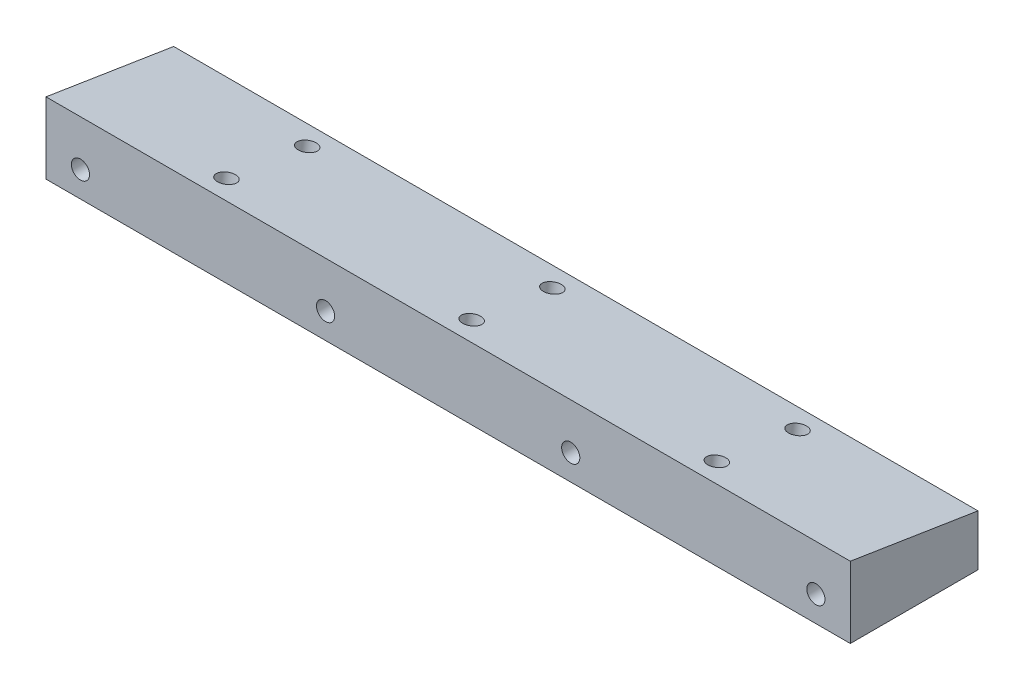
SolidWorks part; units mm, degrees
material "6061-T6 (SS)"
ref_plane "XY" through (0, 0, 0) normal (0, 0, 1) x (1, 0, 0)
ref_plane "XZ" through (0, 0, 0) normal (0, 1, 0) x (1, 0, 0)
ref_plane "YZ" through (0, 0, 0) normal (1, 0, 0) x (0, 0, -1)
ref_axis "X" through (-5, 0, 0) along (1, 0, 0)
ref_axis "Y" through (0, -6.6675, 0) along (0, 1, 0)
ref_axis "Z" through (0, 0, 6.6675) along (0, 0, -1)
sketch "Sketch1" plane through (0, 0, 0) normal (0, 0, 1) x (1, 0, 0)
  line L1 (0, 0) -> (100, 0)
  line L2 (0, 0) -> (0, -6.35)
  line L3 (0, -6.35) -> (100, -6.35)
  line L4 (100, 0) -> (100, -6.35)
  dimension "D1" = 100
  dimension "D2" = 6.35
extrude "Boss-Extrude1" add sketch "Sketch1" along normal blind 15.875
hole_wizard "#4-40 Tapped Hole1" positions "Sketch2" profile "Sketch3" tap size "#4-40" standard "ANSI Inch" end condition through all
sketch "Sketch2" plane through (0, 0, 0) normal (0, 0, -1) x (-1, 0, 0)
  line L0 (-100, -3.175) -> (-95.72, -3.175) construction
  line L1 (-100, 0) -> (-100, -6.35) construction
  line L2 (-95.72, -3.175) -> (-65.24, -3.175) construction
  line L3 (-65.24, -3.175) -> (-34.76, -3.175) construction
  line L4 (-34.76, -3.175) -> (-4.28, -3.175) construction
  line L5 (-4.28, -3.175) -> (0, -3.175) construction
  line L6 (0, 0) -> (0, -6.35) construction
  point P0 (-95.72, -3.175)
  point P2 (-4.28, -3.175)
  point P4 (-34.76, -3.175)
  point P6 (-65.24, -3.175)
  point P25 (-95.6996, -4.4429)
  dimension "D2" = 30.48
sketch "Sketch3" plane through (95.72, -3.175, 0) normal (1, 0, 0) x (0, 1, 0)
  line L0 (0, 0) -> (0, 15.875)
  line L1 (0, 15.875) -> (1.1303, 15.875)
  line L2 (1.1303, 15.875) -> (1.1303, 0)
  line L5 (1.1303, 0) -> (0, 0)
  line L11 (0, -6.35) -> (0, 107.95) construction
  dimension "Thru Tap Drill Dia." = 2.2606
  dimension "Thru Tap Drill Depth" = 15.875
cosmetic thread "Hole Thread1" parameters "D2"=2.8448
cosmetic thread "Hole Thread2" parameters "D2"=2.8448
cosmetic thread "Hole Thread3" parameters "D2"=2.8448
cosmetic thread "Hole Thread4" parameters "D2"=2.8448
sketch "Sketch4" plane through (100, 0, 0) normal (1, 0, 0) x (0, 0, -1)
  line L0 (0, 0) -> (-15.875, 2.5144)
  line L1 (-15.875, 2.5144) -> (-15.875, 0)
  line L2 (-15.875, -6.35) -> (-15.875, 0) construction
  line L3 (-15.875, 0) -> (0, 0) construction
  line L4 (-15.875, 0) -> (0, 0)
  dimension "D1" = 9
extrude "Boss-Extrude2" add sketch "Sketch4" against normal through all
hole_wizard "#4-40 Tapped Hole2" positions "Sketch5" profile "Sketch6" tap size "#4-40" standard "ANSI Inch" end condition through all
sketch "Sketch5" plane through (0, 0, 0) normal (0, 0.9877, -0.1564) x (1, 0, 0)
  line L0 (80.48, -13.1164) -> (80.48, -2.9564) construction
  line L3 (50, -13.1164) -> (50, -2.9564) construction
  line L6 (19.52, -13.1164) -> (19.52, -2.9564) construction
  line L11 (19.52, -8.0364) -> (50, -8.0364) construction
  line L12 (50, -8.0364) -> (80.48, -8.0364) construction
  line L14 (65.24, 0) -> (65.24, -8.0364)
  line L15 (100, 0) -> (0, 0) construction
  line L16 (100, -8.0364) -> (80.48, -8.0364)
  line L17 (100, 0) -> (100, -16.0729) construction
  ellipse E0 centre (65.24, 0.4967) end of major axis (66.3703, 0.4967) minor radius 0.1768 construction
  ellipse E1 centre (65.24, 0.4967) end of major axis (66.3703, 0.4967) minor radius 0.1768
  point P0 (80.48, -13.1164)
  point P2 (80.48, -2.9564)
  point P4 (50, -13.1164)
  point P6 (50, -2.9564)
  point P8 (19.52, -13.1164)
  point P10 (19.52, -2.9564)
  point P61 (100, -9.6437)
  dimension "D1" = 30.48
  dimension "D2" = 10.16
sketch "Sketch6" plane through (80.48, 2.0519, 12.955) normal (1, 0, 0) x (0, 0.1564, 0.9877)
  line L0 (0, 0) -> (0, 8.7552)
  line L1 (0, 8.7552) -> (1.1303, 8.7552)
  line L2 (1.1303, 8.7552) -> (1.1303, 0)
  line L5 (1.1303, 0) -> (0, 0)
  line L11 (0, -6.35) -> (0, 107.95) construction
  dimension "Thru Tap Drill Dia." = 2.2606
  dimension "Thru Tap Drill Depth" = 8.7552
cosmetic thread "Hole Thread5" parameters "D2"=2.8448
cosmetic thread "Hole Thread6" parameters "D2"=2.8448
cosmetic thread "Hole Thread7" parameters "D2"=2.8448
cosmetic thread "Hole Thread8" parameters "D2"=2.8448
cosmetic thread "Hole Thread9" parameters "D2"=2.8448
cosmetic thread "Hole Thread10" parameters "D2"=2.8448
